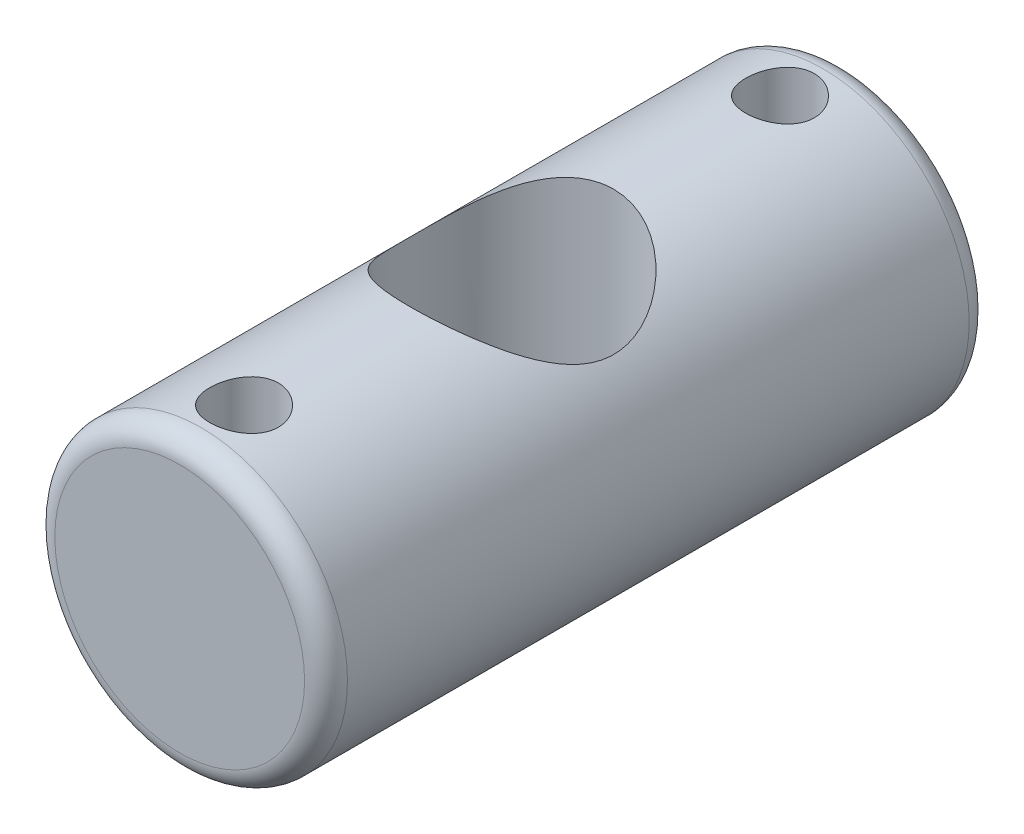
SolidWorks part; units mm, degrees
ref_plane "Front Plane" through (0, 0, 0) normal (0, 0, 1) x (1, 0, 0)
ref_plane "Top Plane" through (0, 0, 0) normal (0, 1, 0) x (1, 0, 0)
ref_plane "Right Plane" through (0, 0, 0) normal (1, 0, 0) x (0, 0, -1)
sketch "Sketch1" plane through (0, 0, 0) normal (0, 0, 1) x (1, 0, 0)
  circle A0 centre (0, 0) radius 6.825
  dimension "D1" = 13.65
extrude "Boss-Extrude1" add sketch "Sketch1" along normal blind 15.5 and the other way blind 15.5
sketch "Sketch2" plane through (0, 0, 0) normal (0, 1, 0) x (1, 0, 0)
  circle A0 centre (0, 0) radius 4.75
  circle A1 centre (0, 0) radius 4.75 construction
  circle A2 centre (0, -12.5) radius 1.6 construction
  circle A3 centre (0, 12.5) radius 1.6 construction
  circle A4 centre (0, -12.5) radius 1.6
  circle A5 centre (0, 12.5) radius 1.6
  dimension "D1" = 9.5
extrude "Cut-Extrude1" cut sketch "Sketch2" against normal blind 10 and the other way blind 10
fillet "Fillet1" radius 1 2 edges at (6.825, 0, 15.5) (6.825, 0, -15.5)
